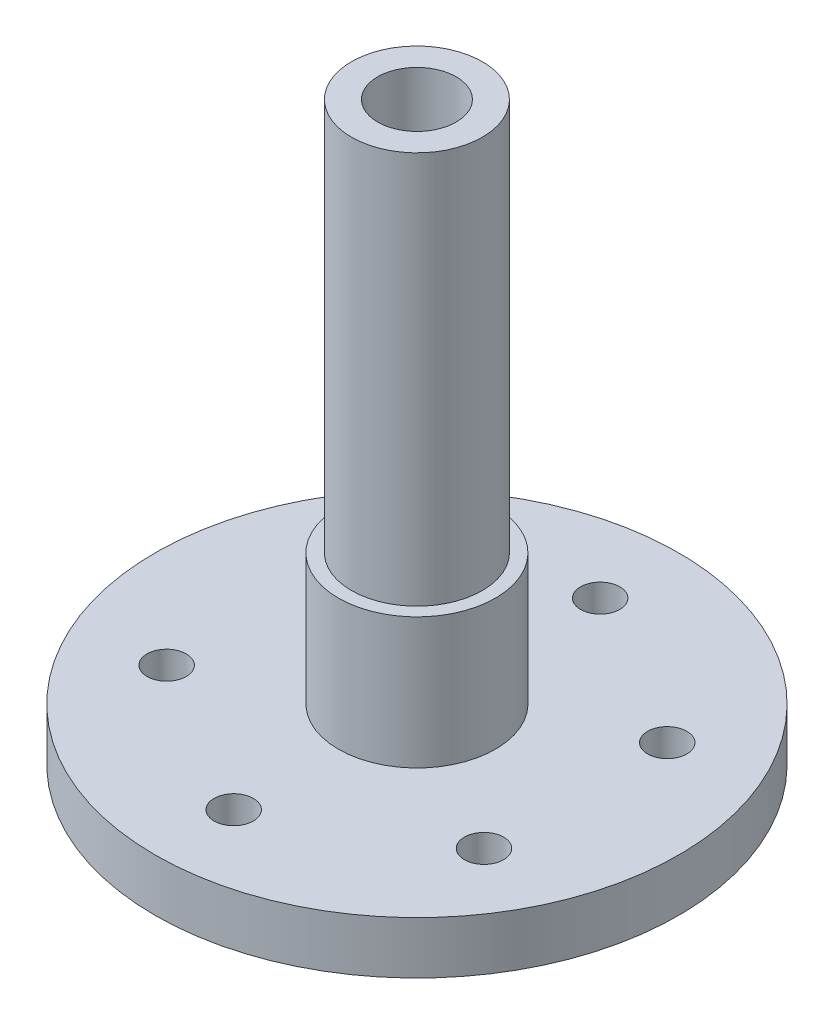
SolidWorks part; units mm, degrees
ref_plane "前视基准面" through (0, 0, 0) normal (0, 0, 1) x (1, 0, 0)
ref_plane "上视基准面" through (0, 0, 0) normal (0, 1, 0) x (1, 0, 0)
ref_plane "右视基准面" through (0, 0, 0) normal (1, 0, 0) x (0, 0, -1)
ref_axis "x轴" through (88.99, 0, 0) along (-1, 0, 0)
ref_axis "y轴" through (0, 0, -88.99) along (0, 0, 1)
ref_axis "z轴" through (0, -44, 0) along (0, 1, 0)
sketch "草图1" plane through (0, 0, 0) normal (0, 1, 0) x (1, 0, 0)
  circle A0 centre (0, 0) radius 20
  circle A1 centre (0, 0) radius 14 construction
  circle A2 centre (0, 14) radius 1.5
  circle A3 centre (12.1244, 7) radius 1.5
  circle A4 centre (12.1244, -7) radius 1.5
  circle A5 centre (0, -14) radius 1.5
  circle A6 centre (-12.1244, -7) radius 1.5
  circle A7 centre (-12.1244, 7) radius 1.5
  circle A8 centre (0, 0) radius 3
  point P19 (0, 0)
  dimension "D1" = 6
extrude "凸台-拉伸1" add sketch "草图1" along normal blind 4
sketch "草图2" plane through (0, 4, 0) normal (0, 1, 0) x (1, 0, 0)
  circle A0 centre (0, 0) radius 3
  circle A1 centre (0, 0) radius 6
extrude "凸台-拉伸2" add sketch "草图2" along normal blind 10
sketch "草图3" plane through (0, 14, 0) normal (0, 1, 0) x (1, 0, 0)
  circle A0 centre (0, 0) radius 3
  circle A1 centre (0, 0) radius 5
extrude "凸台-拉伸3" add sketch "草图3" along normal blind 30
